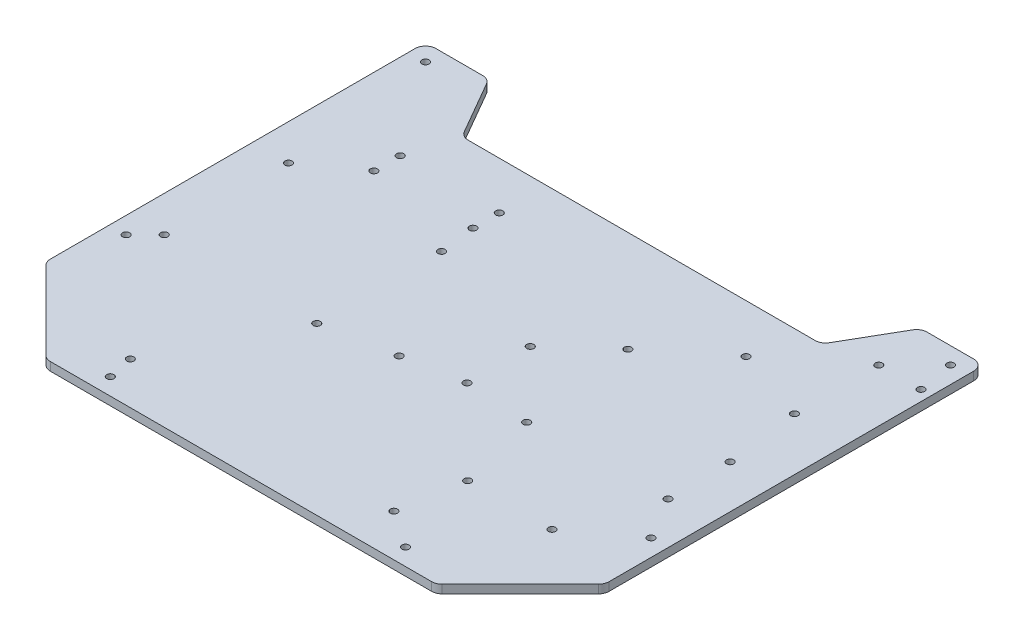
SolidWorks part; units mm, degrees
material "Acier non allié"
ref_plane "Front" through (0, 0, 0) normal (0, 0, 1) x (1, 0, 0)
ref_plane "Top" through (0, 0, 0) normal (0, 1, 0) x (1, 0, 0)
ref_plane "Right" through (0, 0, 0) normal (1, 0, 0) x (0, 0, -1)
sketch "Main scetch" plane through (0, 0, 0) normal (0, 1, 0) x (1, 0, 0)
  line L1 (0, 0) -> (132.5, 0) construction
  line L2 (0, 0) -> (0, 220) construction
  line L3 (0, 220) -> (132.5, 220) construction
  line L4 (132.5, 0) -> (132.5, 220) construction
  line L13 (-92.5, 0) -> (92.5, 0)
  line L14 (92.5, 0) -> (132.5, 40)
  line L15 (132.5, 40) -> (132.5, 220)
  line L16 (132.5, 220) -> (102.5, 220)
  line L17 (102.5, 220) -> (85.1795, 190)
  line L18 (85.1795, 190) -> (-85.1795, 190)
  line L19 (-102.5, 220) -> (-85.1795, 190)
  line L20 (-132.5, 220) -> (-102.5, 220)
  line L21 (-132.5, 40) -> (-132.5, 220)
  line L22 (-92.5, 0) -> (-132.5, 40)
  point P11 (0, 190)
  dimension "132.5" = 132.5
  dimension "D2" = 220
  dimension "D1" = 40
  dimension "D3" = 40
  dimension "D4" = 30
  dimension "D5" = 60
  dimension "D6" = 30
extrude "Main extrusion" add sketch "Main scetch" along normal blind 4
fillet "Congé1" radius 5 10 edges at (-132.5, 2, -40) (-92.5, 2, 0) (92.5, 2, 0) (132.5, 2, -40) (132.5, 2, -220) (102.5, 2, -220) (85.1795, 2, -190) (-85.1795, 2, -190) (-102.5, 2, -220) (-132.5, 2, -220)
sketch "Esquisse1" plane through (0, 4, 0) normal (0, 1, 0) x (1, 0, 0)
  line L0 (0, 0) -> (0, 218.5516) construction
  line L1 (132.5, 42.0711) -> (132.5, 215) construction
  line L2 (127.5, 220) -> (105.3868, 220) construction
  line L3 (-90.4289, 0) -> (90.4289, 0) construction
  circle A0 centre (70, 8) radius 1
  circle A1 centre (124.5, 70) radius 1
  circle A2 centre (124.5, 212) radius 1
  circle A3 centre (-124.5, 212) radius 1
  circle A4 centre (-124.5, 70) radius 1
  circle A5 centre (-70, 8) radius 1
  dimension "D1" = 2
  dimension "D2" = 2
  dimension "D3" = 2
  dimension "D4" = 8
  dimension "D5" = 8
  dimension "D6" = 8
  dimension "D7" = 8
  dimension "D8" = 70
  dimension "D9" = 70
extrude "Enlèv. mat.-Extru.1" cut sketch "Esquisse1" against normal through all
hole_wizard "Dégagement M31" positions "Esquisse2" profile "Esquisse3" hole size "M3" standard "ISO" end condition through all
sketch "Esquisse2" plane through (0, 4, 0) normal (0, 1, 0) x (1, 0, 0)
  point P0 (-124.5, 212)
  point P3 (-124.5, 70)
  point P6 (-70, 8)
  point P9 (70, 8)
  point P12 (124.5, 70)
  point P15 (124.5, 212)
sketch "Esquisse3" plane through (-124.5, 4, -212) normal (1, 0, 0) x (0, 0, 1)
  line L0 (0, 0) -> (0, 4)
  line L1 (0, 4) -> (1.7, 4)
  line L2 (1.7, 4) -> (1.7, 0)
  line L5 (1.7, 0) -> (0, 0)
  line L11 (0, -6.35) -> (0, 107.95) construction
  dimension "Diamètre du perçage jusqu'au prochain" = 3.4
  dimension "Profondeur du perçage jusqu'au prochain" = 4
sketch "Esquisse4" plane through (0, 4, 0) normal (0, 1, 0) x (1, 0, 0)
  line L0 (-132.5, 215) -> (-132.5, 42.0711) construction
  line L2 (82.2927, 190) -> (-82.2927, 190) construction
  line L3 (132.5, 42.0711) -> (132.5, 215) construction
  line L4 (-90.4289, 0) -> (90.4289, 0) construction
  line L5 (127.5, 220) -> (105.3868, 220) construction
  circle A1 centre (-68.5, 185) radius 1 construction
  circle A5 centre (72.5, 167) radius 1
  circle A6 centre (41.5, 142) radius 1
  circle A7 centre (107.5, 155) radius 1
  circle A8 centre (127.5, 195) radius 1
  circle A9 centre (112, 120) radius 1
  circle A10 centre (112.5, 90) radius 1
  circle A11 centre (17.2, 120) radius 1
  circle A12 centre (17.2, 90) radius 1
  circle A13 centre (47.5, 88) radius 1
  circle A14 centre (57.5, 50) radius 1
  circle A15 centre (97.5, 50) radius 1
  circle A16 centre (52.5, 20) radius 1
  circle A17 centre (-10, 85) radius 1
  circle A18 centre (-72.5, 20) radius 1
  circle A19 centre (107.5, 195) radius 1
  circle A23 centre (-115.5, 138) radius 1
  circle A24 centre (-42.86, 138) radius 1
  circle A25 centre (-115.5, 79.07) radius 1
  circle A26 centre (-42.8904, 78.82) radius 1
  circle A27 centre (-92, 167.5) radius 1
  circle A28 centre (-45, 167.5) radius 1
  circle A29 centre (-92, 155) radius 1
  circle A30 centre (-45, 155) radius 1
  dimension "D4" = 2
  dimension "D13" = 2
  dimension "D16" = 2
  dimension "D19" = 2
  dimension "D24" = 2
  dimension "D25" = 2
  dimension "D28" = 2
  dimension "D30" = 2
  dimension "D32" = 2
  dimension "D36" = 2
  dimension "D37" = 2
  dimension "D40" = 2
  dimension "D48" = 2
  dimension "D49" = 2
  dimension "D50" = 2
  dimension "D52" = 2
  dimension "D11" = 2
  dimension "D12" = 2
  dimension "D65" = 2
  dimension "D66" = 2
  dimension "D58" = 2
  dimension "D61" = 2
  dimension "D70" = 2
  dimension "D71" = 2
  dimension "D14" = 205
  dimension "D15" = 23
  dimension "D20" = 25
  dimension "D21" = 65
  dimension "D22" = 5
  dimension "D23" = 25
  dimension "D26" = 20.5
  dimension "D27" = 100
  dimension "D29" = 30
  dimension "D31" = 115.3
  dimension "D33" = 115.3
  dimension "D34" = 132
  dimension "D35" = 85
  dimension "D38" = 50
  dimension "D39" = 75
  dimension "D41" = 35
  dimension "D42" = 80
  dimension "D43" = 20
  dimension "D44" = 20
  dimension "D45" = 205
  dimension "D46" = 85
  dimension "D47" = 142.5
  dimension "D51" = 25
  dimension "D53" = 25
  dimension "D54" = 5
  dimension "D55" = 64
  dimension "D7" = 59.18
  dimension "D8" = 72.64
  dimension "D9" = 58.93
  dimension "D10" = 72.61
  dimension "D67" = 17
  dimension "D68" = 138
  dimension "D56" = 23.5
  dimension "D57" = 23.5
  dimension "D59" = 17.5
  dimension "D60" = 17.5
  dimension "D62" = 12.5
  dimension "D63" = 12.5
  dimension "D64" = 23.5
  dimension "D69" = 23.5
  dimension "D17" = 25
  dimension "D18" = 31
extrude "Enlèv. mat.-Extru.2" cut sketch "Esquisse4" against normal through all
hole_wizard "Dégagement M32" positions "Esquisse5" profile "Esquisse6" hole size "M3" standard "ISO" end condition through all
sketch "Esquisse5" plane through (0, 4, 0) normal (0, 1, 0) x (1, 0, 0)
  point P9 (17.2, 120)
  point P18 (41.5, 142)
  point P21 (72.5, 167)
  point P24 (107.5, 155)
  point P27 (127.5, 195)
  point P30 (112, 120)
  point P33 (112.5, 90)
  point P36 (47.5, 88)
  point P39 (17.2, 90)
  point P42 (57.5, 50)
  point P45 (97.5, 50)
  point P48 (-10, 85)
  point P51 (-72.5, 20)
  point P54 (52.5, 20)
  point P57 (107.5, 195)
  point P86 (-115.5, 138)
  point P89 (-42.86, 138)
  point P92 (-115.5, 79.07)
  point P95 (-42.8904, 78.82)
  point P102 (-92, 167.5)
  point P105 (-92, 155)
  point P108 (-45, 155)
  point P111 (-45, 167.5)
sketch "Esquisse6" plane through (17.2, 4, -120) normal (1, 0, 0) x (0, 0, 1)
  line L0 (0, 0) -> (0, 4)
  line L1 (0, 4) -> (1.7, 4)
  line L2 (1.7, 4) -> (1.7, 0)
  line L5 (1.7, 0) -> (0, 0)
  line L11 (0, -6.35) -> (0, 107.95) construction
  dimension "Diamètre du perçage jusqu'au prochain" = 3.4
  dimension "Profondeur du perçage jusqu'au prochain" = 4
equation "\"WIDTH\"= 300mm'Total width of the robot"
equation "\"LENGTH\"= 220mm'Total length of the robot"
equation "\"D2@Main scetch\" = \"LENGTH\""
equation "\"CUT_DEPTH\"= 45mm'Depth of the cut on the edges of the plate"
equation "\"Plate_th\"= 3mm'Thickness of the plate"
equation "\"D1\"= \"Plate_th\""
equation "\"D47@Esquisse4\"=(80+205)/2"
